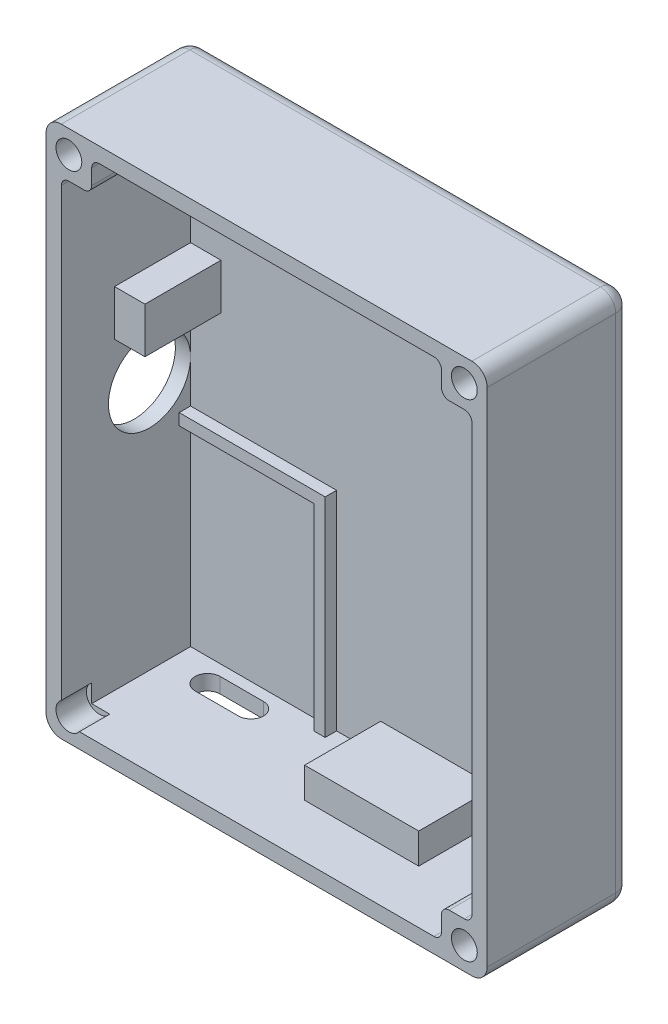
SolidWorks part; units mm, degrees
ref_plane "Спереди" through (0, 0, 0) normal (0, 0, 1) x (1, 0, 0)
ref_plane "Сверху" through (0, 0, 0) normal (0, 1, 0) x (1, 0, 0)
ref_plane "Справа" through (0, 0, 0) normal (1, 0, 0) x (0, 0, -1)
sketch "Эскиз1" plane through (0, 0, 0) normal (0, 0, 1) x (1, 0, 0)
  line L1 (-29, -35) -> (29, -35)
  line L2 (-29, -35) -> (-29, 35)
  line L3 (-29, 35) -> (29, 35)
  line L4 (29, -35) -> (29, 35)
  line L5 (-29, -35) -> (29, 35) construction
  line L6 (-29, 35) -> (29, -35) construction
  point P0 (0, 0)
  dimension "D1" = 58
  dimension "D2" = 70
extrude "Бобышка-Вытянуть1" add sketch "Эскиз1" along normal blind 18.9
sketch "Эскиз2" plane through (0, 0, 18.9) normal (0, 0, 1) x (1, 0, 0)
  line L0 (29, 35) -> (-29, 35) construction
  line L1 (-27, -33) -> (27, -33)
  line L2 (-27, -33) -> (-27, 33)
  line L3 (-27, 33) -> (27, 33)
  line L4 (27, -33) -> (27, 33)
  line L5 (-27, -33) -> (27, 33) construction
  line L6 (-27, 33) -> (27, -33) construction
  line L7 (-29, 35) -> (-29, -35) construction
  line L8 (0, 33) -> (0, -33) construction
  line L9 (-27, 0) -> (27, 0) construction
  line L11 (27, 29) -> (23, 29)
  line L12 (-27, 33) -> (-23, 33)
  line L13 (-27, 33) -> (-27, 29)
  line L14 (-27, 29) -> (-23, 29)
  line L15 (-23, 33) -> (-23, 29)
  line L16 (23, 33) -> (23, 29)
  line L17 (27, 33) -> (23, 33)
  line L18 (27, 33) -> (27, 29)
  line L19 (27, -33) -> (23, -33)
  line L20 (23, -33) -> (23, -29)
  line L21 (27, -29) -> (23, -29)
  line L22 (27, -33) -> (27, -29)
  line L23 (-27, -29) -> (-23, -29)
  line L24 (-23, -33) -> (-23, -29)
  line L25 (-27, -33) -> (-23, -33)
  line L26 (-27, -33) -> (-27, -29)
  circle A0 centre (-26, 32) radius 1.7
  circle A1 centre (26, 32) radius 1.7
  circle A2 centre (26, -32) radius 1.7
  circle A3 centre (-26, -32) radius 1.7
  point P0 (0, 0)
  point P15 (25, 29)
  dimension "D7" = 3.4
  dimension "D1" = 2
  dimension "D2" = 2
  dimension "D3" = 4
  dimension "D4" = 4
  dimension "D5" = 3
  dimension "D6" = 3
  dimension "D8" = 58
extrude "Вырез-Вытянуть1" cut sketch "Эскиз2" against normal blind 17 contours L24 L1 L20 L21 L4 L11 L16 L3 L15 L14 L2 L23 | L26 A3 L25 L24 L23 | A3 L2 L1 region at (0, 0, 18.9) region at (-24.4949, -30.4949, 18.9) region at (-25.7455, -31.7455, 18.9)
extrude "Вырез-Вытянуть2" cut sketch "Эскиз2<3>" against normal blind 4 contours A0 | A3 | A2 | A1
sketch "Эскиз2<3>" plane through (0, 0, 18.9) normal (0, 0, 1) x (1, 0, 0) same geometry as "Эскиз2"
fillet "Скругление1" radius 1 9 edges at (23, -33, 10.4) (23, -29, 10.4) (27, -29, 10.4) (23, 33, 10.4) (27, 29, 10.4) (-23, 33, 10.4) (-27, 29, 10.4) (23, 29, 10.4) (-23, 29, 10.4)
fillet "Скругление2" radius 2 8 edges at (0, 35, 0) (-29, 0, 0) (0, -35, 0) (29, 0, 0) (29, 35, 9.45) (-29, 35, 9.45) (-29, -35, 9.45) (29, -35, 9.45)
sketch "Эскиз4" plane through (0, 0, 1.9) normal (0, 0, 1) x (1, 0, 0)
  line L0 (-27, -33) -> (-27, 28) construction
  line L1 (-27, 13) -> (-23, 13)
  line L2 (-27, 13) -> (-27, 7)
  line L3 (-27, 7) -> (-23, 7)
  line L4 (-23, 13) -> (-23, 7)
  line L5 (-22, 33) -> (22, 33) construction
  line L6 (-27, -33) -> (22, -33) construction
  line L7 (-2, -33) -> (13, -33)
  line L8 (-2, -33) -> (-2, -29)
  line L9 (-2, -29) -> (13, -29)
  line L10 (13, -33) -> (13, -29)
  line L12 (14, 33) -> (5, 33)
  line L13 (14, 33) -> (14, 27)
  line L14 (14, 27) -> (5, 27)
  line L15 (5, 33) -> (5, 27)
  line L16 (-27, -30.6252) -> (-27, 28) construction
  circle A0 centre (-20.9, 21.7) radius 1.5
  line M4 (-27, -33) -> (22, -33)
  line M16 (22, 33) -> (-22, 33)
  line M22 (-27, 28) -> (-27, -33)
  dimension "D10" = 3
  dimension "D11" = 54.7
  dimension "D2" = 6
  dimension "D3" = 4
  dimension "D4" = 60
  dimension "D5" = 32
  dimension "D6" = 9
  dimension "D7" = 4
  dimension "D8" = 15
  dimension "D9" = 25
  dimension "D12" = 6.1
  dimension "D13" = 40
extrude "Вырез-Вытянуть3" cut sketch "Эскиз4" against normal blind 2 contours A0 region at (-20.9, 21.7, 1.9)
extrude "Бобышка-Вытянуть2" add sketch "Эскиз4<3>" along normal blind 10 contours L10 L9 L8 M4 | L4 L1 L3 M22 | L15 L14 L13 M16 region at (5.5, -31, 1.9) region at (-25, 10, 1.9) region at (9.5, 30, 1.9)
sketch "Эскиз4<3>" plane through (0, 0, 1.9) normal (0, 0, 1) x (1, 0, 0) same geometry as "Эскиз4"
sketch "Эскиз6" plane through (0, 0, 1.9) normal (0, 0, 1) x (1, 0, 0)
  line L5 (27, -28) -> (27, 28) construction
  line L8 (-27, -33) -> (-2, -33) construction
  line L9 (-27, -33) -> (17, -33)
  line L10 (-27, -33) -> (-27, 30)
  line L11 (-27, 30) -> (17, 30)
  line L12 (17, -33) -> (17, 30)
  line L13 (-27, -30.6252) -> (-27, 28) construction
  dimension "D1" = 44
  dimension "D2" = 63
  dimension "D3" = 0
  dimension "D4" = 0
  dimension "D5" = 10
sketch "Эскиз7" plane through (-29, 0, 0) normal (-1, 0, 0) x (0, 0, 1)
  line L0 (1.9, -33) -> (1.9, 30) construction
  line L1 (18.9, 0) -> (2, 0) construction
  line L2 (18.9, 33) -> (18.9, -33) construction
  line L3 (2, 33) -> (2, -33) construction
  line L4 (2, -33) -> (18.9, -33) construction
  circle A0 centre (7.3, 0) radius 5.4
  point P10 (1.9, -1.5)
  dimension "D1" = 10.8
  dimension "D2" = 0
  dimension "D3" = 5.4
  dimension "D4" = 33
extrude "Вырез-Вытянуть4" cut sketch "Эскиз7" against normal blind 2
sketch "Эскиз8" plane through (0, -35, 0) normal (0, -1, 0) x (1, 0, 0)
  line L0 (-21.65, 5) -> (-15.95, 5) construction
  line L1 (-21.65, 6.65) -> (-15.95, 6.65)
  line L2 (-21.65, 3.35) -> (-15.95, 3.35)
  line L3 (-27, 1.9) -> (17, 1.9) construction
  line L4 (-27, 18.9) -> (-27, 2) construction
  arc A0 (-21.65, 6.65) -> (-21.65, 3.35) centre (-21.65, 5) ccw
  arc A1 (-15.95, 3.35) -> (-15.95, 6.65) centre (-15.95, 5) ccw
  point P2 (-18.8, 5)
  point P7 (-18.8, 3.35)
  point P14 (-21.65, 6.8)
  dimension "D3" = 5.35
  dimension "D1" = 1.45
  dimension "D2" = 3.3
  dimension "D4" = 5.7
extrude "Вырез-Вытянуть5" cut sketch "Эскиз8" against normal blind 2
sketch "Эскиз10" plane through (0, 0, 1.9) normal (0, 0, 1) x (1, 0, 0)
  line L0 (-27, -33) -> (17, -33) construction
  line L1 (-9.3, -33) -> (-27, -33)
  line L2 (-9.3, -33) -> (-9.3, -7.1)
  line L3 (-9.3, -7.1) -> (-27, -7.1)
  line L4 (-27, -33) -> (-27, -7.1)
  line L5 (-27, -33) -> (-27, 30) construction
  line L7 (-7.8, -33) -> (-27, -33)
  line L8 (-7.8, -33) -> (-7.8, -5.6)
  line L9 (-7.8, -5.6) -> (-27, -5.6)
  line L10 (-27, -33) -> (-27, -5.6)
  dimension "D1" = 17.7
  dimension "D2" = 25.9
  dimension "D3" = 1.5
  dimension "D4" = 1.5
extrude "Бобышка-Вытянуть3" add sketch "Эскиз10" along normal blind 1.5 contours L8 L9 L3 L2 region at (-8.9654, -20.05, 1.9)
